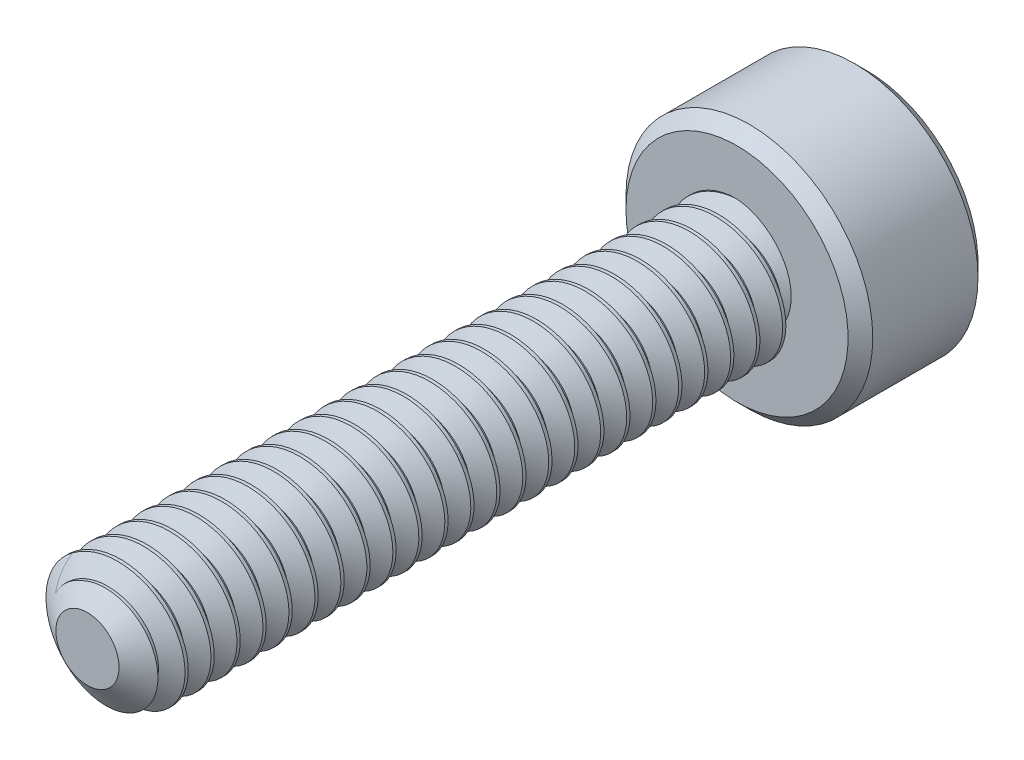
SolidWorks part; units mm, degrees
other "DetailItem1"
ref_plane "Front Plane" through (0, 0, 0) normal (0, 0, 1) x (1, 0, 0)
ref_plane "Top Plane" through (0, 0, 0) normal (0, 1, 0) x (1, 0, 0)
ref_plane "Right Plane" through (0, 0, 0) normal (1, 0, 0) x (0, 0, -1)
sketch "Sketch1" plane through (0, 0, 0) normal (0, 0, 1) x (1, 0, 0)
  circle A0 centre (0, 0) radius 1
  dimension "OD" = 2
extrude "Extrude1" add sketch "Sketch1" against normal blind 10
sketch "Sketch2" plane through (0, 0, 0) normal (0, 0, 1) x (1, 0, 0)
  circle A0 centre (0, 0) radius 1 construction
  circle A1 centre (0, 0) radius 1
curve "Helix/Spiral1" pitch 0.4 height 10.4 radius 1 centre (0, 0, 0) axis (0, 0, -1) start towards (0, 1, 0) parameters "pitch"=0.4
sketch "Sketch3" plane through (0, 0, 0) normal (1, 0, 0) x (0, 0, -1)
  line L0 (-0.35, 1) -> (-0.2, 0.7402)
  line L1 (-0.2, 0.7402) -> (-0.15, 0.7402)
  line L2 (-0.15, 0.7402) -> (0, 1)
  line L3 (-0.35, 1) -> (0, 1)
  line L4 (-0.175, 1) -> (-0.175, 0.7402) construction
  line L5 (-0.275, 0.8701) -> (-0.075, 0.8701) construction
  line L6 (0, 1) -> (0, -1) construction
  dimension "D1" = 0.05
  dimension "D2" = 0.2
  dimension "D3" = 60
sweep "Cut-Sweep1" cut profiles "Sketch3" path "Helix/Spiral1"
sketch "Sketch4" plane through (0, 0, 0) normal (1, 0, 0) x (0, 0, -1)
  line L0 (0.3598, 1) -> (0, 0.4862)
  line L1 (0, 0.4862) -> (0, 1)
  line L2 (0.3598, 1) -> (0, 1)
  line L3 (-0.35, 1) -> (0, 1) construction
  line L4 (0, 0) -> (7.0209, 0) construction
  dimension "D1" = 55
  dimension "D2" = 0.254
revolve "Cut-Revolve1" cut sketch "Sketch4" angle 360 about L4
sketch "Sketch6" plane through (0, 0, -10) normal (0, 0, -1) x (-1, 0, 0)
  circle A0 centre (0, 0) radius 1.9
  dimension "head dia" = 3.8
extrude "Extrude2" add sketch "Sketch6" along normal blind 2
sketch "Sketch7" plane through (0, 0, -12) normal (0, 0, -1) x (-1, 0, 0)
  line L1 (0, 0.866) -> (-0.75, 0.433)
  line L2 (-0.75, 0.433) -> (-0.75, -0.433)
  line L3 (-0.75, -0.433) -> (0, -0.866)
  line L4 (0, -0.866) -> (0.75, -0.433)
  line L5 (0.75, -0.433) -> (0.75, 0.433)
  line L6 (0.75, 0.433) -> (0, 0.866)
  circle A0 centre (0, 0) radius 0.75 construction
  dimension "hex dia" = 1.5
extrude "Cut-Extrude1" cut sketch "Sketch7" against normal blind 1.125
sketch "Sketch8" plane through (0, 0, -12) normal (0, 0, -1) x (-1, 0, 0)
  circle A0 centre (0, 0) radius 0.866
extrude "Cut-Extrude2" cut sketch "Sketch8" against normal through all draft 45
chamfer "Chamfer1" distance 0.19 angle 45 2 edges at (-1.9, 0, -12) (-1.9, 0, -10)
sketch "Sketch10" plane through (0, 0, -10) normal (0, 0, 1) x (1, 0, 0)
  circle A1 centre (0, 0) radius 1
  circle A2 centre (0, 0) radius 1
  dimension "D1" = 0
ref_plane "Plane1" through (0, 0, 0) normal (0, 0, 1) x (1, 0, 0)
extrude "partial thread" [suppressed] add sketch "Sketch10" along normal up to surface (2 mm away) separate body up to plane "Plane1"
chamfer "Chamfer2" [suppressed] distance 0.04 angle 45
combine bodies "Combine1" [suppressed] operation type add bodies to combine 107 108
sketch "Sketch9" plane through (0, 0, 0) normal (1, 0, 0) x (0, 0, -1)
  line L0 (0, 1) -> (0, -1) construction
  line L1 (1, 1) -> (1, -1) construction
  dimension "D1" = 1
  dimension "D4" = 0.635
  dimension "D5" = 0.3302
equation "\"D3@Helix/Spiral1\" = \"screw length@Extrude1\"+\"pitch@Helix/Spiral1\""
equation "\"D1@Sketch3\" = \"pitch@Helix/Spiral1\"*.125"
equation "\"D2@Sketch3\" = \"pitch@Helix/Spiral1\"*.5"
equation "\"D1@Cut-Extrude1\" = \"hex dia@Sketch7\"*.75"
equation "\"D1@Chamfer1\" = \"head dia@Sketch6\"*.05"
equation "\"D1@Sketch9\" = \"pitch@Helix/Spiral1\"*2.5"
equation "\"D1@Chamfer2\"=\"OD@Sketch1\"*.02"
